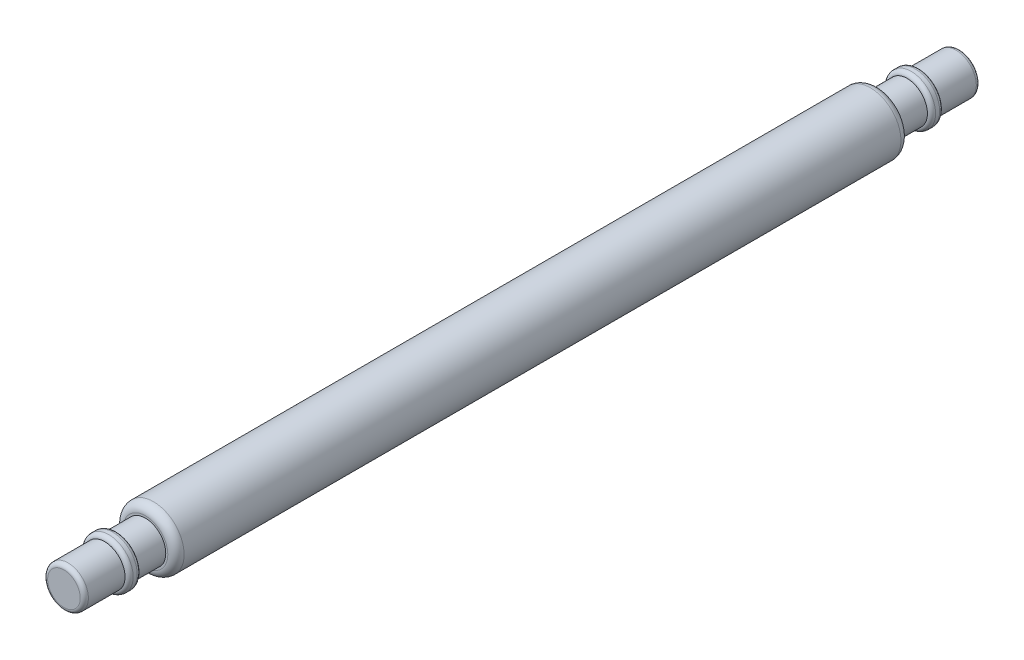
SolidWorks part; units mm, degrees
ref_plane "Front Plane" through (0, 0, 0) normal (0, 0, 1) x (1, 0, 0)
ref_plane "Top Plane" through (0, 0, 0) normal (0, 1, 0) x (1, 0, 0)
ref_plane "Right Plane" through (0, 0, 0) normal (1, 0, 0) x (0, 0, -1)
sketch "Sketch1" plane through (0, 0, 0) normal (0, 0, 1) x (1, 0, 0)
  circle A0 centre (0, 0) radius 0.75
  dimension "D1" = 1.5
extrude "Boss-Extrude1" add sketch "Sketch1" along normal mid plane 22
sketch "Sketch2" plane through (0, 0, 11) normal (0, 0, 1) x (1, 0, 0)
  circle A0 centre (0, 0) radius 0.5
  circle A1 centre (0, 0) radius 1.3894
  dimension "D1" = 1
extrude "Cut-Extrude1" cut sketch "Sketch2" against normal blind 2
sketch "Sketch3" plane through (0, 0, -11) normal (0, 0, -1) x (-1, 0, 0)
  circle A0 centre (0, 0) radius 0.5
  circle A1 centre (0, 0) radius 1.1531
  dimension "D1" = 1
extrude "Cut-Extrude2" cut sketch "Sketch3" against normal blind 2
sketch "Sketch4" plane through (0, 0, -11) normal (0, 0, -1) x (-1, 0, 0)
  circle A0 centre (0, 0) radius 0.5
  circle A1 centre (0, 0) radius 0.6
  dimension "D1" = 1.2
extrude "Boss-Extrude2" add sketch "Sketch4" against normal blind 0.3 from offset 1 offset against normal yes
fillet "Fillet1" radius 0.2 2 edges at (0.75, 0, 9) (-0.75, 0, -9)
fillet "Fillet2" radius 0.1 3 edges at (-0.6, 0, -10) (-0.6, 0, -9.7) (-0.5, 0, -11)
mirror "Mirror1" about plane through (0, 0, 0) normal (0, 0, 1) of "Boss-Extrude2"
fillet "Fillet3" radius 0.1 3 edges at (-0.6, 0, 10) (-0.6, 0, 9.7) (0.5, 0, 11)
